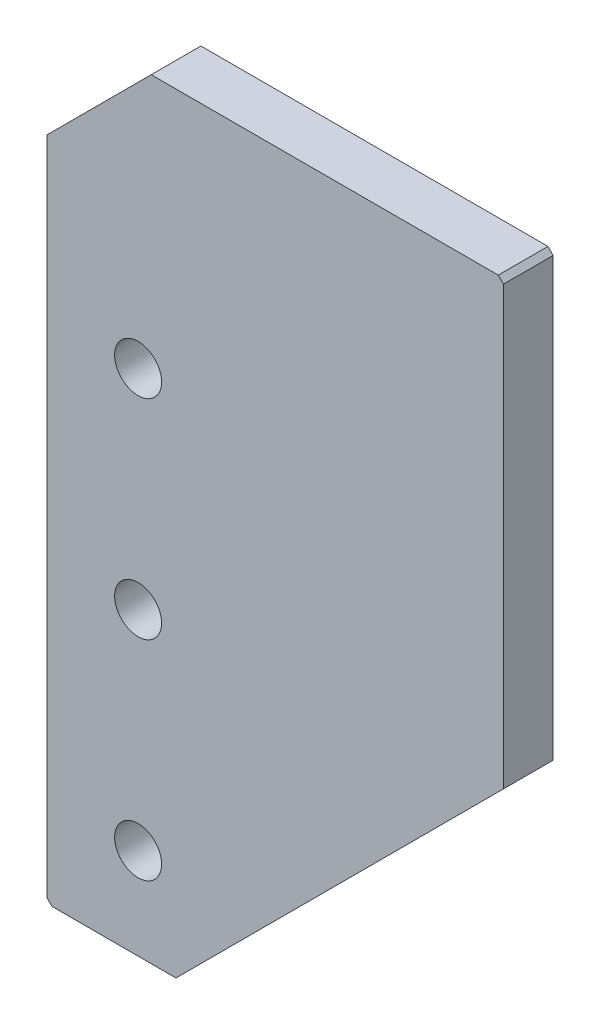
SolidWorks part; units mm, degrees
material "6061-T6 (SS)"
ref_plane "Front Plane" through (0, 0, 0) normal (0, 0, 1) x (1, 0, 0)
ref_plane "Top Plane" through (0, 0, 0) normal (0, 1, 0) x (1, 0, 0)
ref_plane "Right Plane" through (0, 0, 0) normal (1, 0, 0) x (0, 0, -1)
sketch "Sketch1" plane through (0, 0, 0) normal (0, 0, 1) x (1, 0, 0)
  line L0 (-25, 19.9957) -> (-25, -0.608) construction
  line L1 (-35, -0.608) -> (-35, 13.6457) construction
  line L2 (-55, 60) -> (-55, 20) construction
  line L3 (-55, 20) -> (-55, -20) construction
  line L4 (55, 0) -> (-55, 0) construction
  line L5 (-72.5, -37.5) -> (-47.7513, -37.5)
  line L6 (-47.7513, -37.5) -> (15, 25.2513)
  line L7 (15, 25.2513) -> (15, 110)
  line L8 (15, 110) -> (-52.5, 110)
  line L9 (-72.5, 90) -> (-72.5, -37.5)
  line L10 (-52.5, 110) -> (-72.5, 90)
  point P8 (-55, 0)
  point P13 (-72.5, 110)
  dimension "D1" = 10
  dimension "D2" = 25
  dimension "D3" = 40
  dimension "D4" = 20
  dimension "D5" = 17.5
  dimension "D6" = 17.5
  dimension "D7" = 17.5
  dimension "D8" = 110
  dimension "D9" = 90
  dimension "D10" = 45
  dimension "D11" = 50
extrude "Boss-Extrude1" add sketch "Sketch1" along normal mid plane 9.525
hole_wizard "M8 Clearance Hole1" positions "Sketch2" profile "Sketch3" hole size "M8" standard "ANSI Metric" end condition up to next
sketch "Sketch2" plane through (0, 0, 4.7625) normal (0, 0, 1) x (1, 0, 0)
  point P0 (-55, 60)
  point P3 (-55, 20)
  point P6 (-55, -20)
sketch "Sketch3" plane through (-55, 60, 4.7625) normal (1, 0, 0) x (0, -1, 0)
  line L0 (0, 0) -> (0, 9.525)
  line L1 (0, 9.525) -> (4.5, 9.525)
  line L2 (4.5, 9.525) -> (4.5, 0)
  line L5 (4.5, 0) -> (0, 0)
  line L11 (0, -6.35) -> (0, 107.95) construction
  dimension "Thru Hole Dia." = 9
  dimension "Thru Hole Depth" = 9.525
chamfer "Chamfer1" distance 1 2 edges at (15, 110, 0) (-72.5, -37.5, 0)
